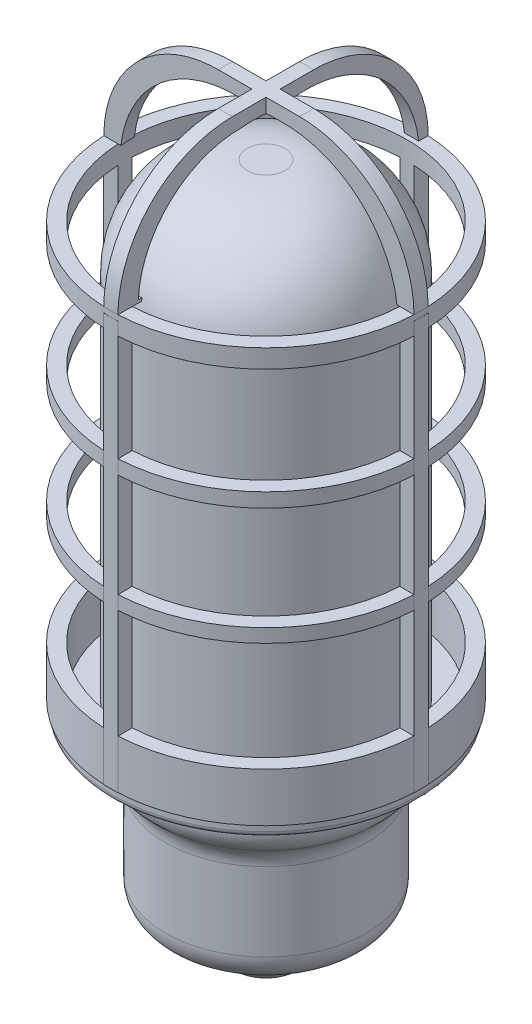
SolidWorks part; units mm, degrees
ref_plane "Front Plane" through (0, 0, 0) normal (0, 0, 1) x (1, 0, 0)
ref_plane "Top Plane" through (0, 0, 0) normal (0, 1, 0) x (1, 0, 0)
ref_plane "Right Plane" through (0, 0, 0) normal (1, 0, 0) x (0, 0, -1)
sketch "Sketch1" plane through (0, 0, 0) normal (0, 1, 0) x (1, 0, 0)
  circle A0 centre (0, 0) radius 72.39
  circle A1 centre (0, 0) radius 65.786
  dimension "D1" = 144.78
  dimension "D2" = 131.572
extrude "Boss-Extrude1" add sketch "Sketch1" along normal blind 22.86
ref_plane "Plane1" through (0, 73.66, 0) normal (0, 1, 0) x (1, 0, 0)
sketch "Sketch2" plane through (0, 73.66, 0) normal (0, 1, 0) x (1, 0, 0)
  circle A0 centre (0, 0) radius 72.39
  dimension "D1" = 144.78
extrude "Boss-Extrude2" add sketch "Sketch2" along normal blind 6.35 separate body
ref_plane "Plane2" through (0, 128.27, 0) normal (0, 1, 0) x (1, 0, 0)
sketch "Sketch3" plane through (0, 128.27, 0) normal (0, 1, 0) x (1, 0, 0)
  circle A0 centre (0, 0) radius 72.39
extrude "Boss-Extrude3" add sketch "Sketch3" along normal blind 6.604 separate body
ref_plane "Plane3" through (0, 184.404, 0) normal (0, 1, 0) x (1, 0, 0)
sketch "Sketch4" plane through (0, 184.404, 0) normal (0, 1, 0) x (1, 0, 0)
  circle A0 centre (0, 0) radius 72.39
extrude "Boss-Extrude4" add sketch "Sketch4" along normal blind 6.096 separate body
sketch "Sketch6" plane through (0, 0, 0) normal (0, -1, 0) x (1, 0, 0)
  circle A0 centre (0, 0) radius 65.786
  dimension "D1" = 131.572
extrude "Cut-Extrude1" cut sketch "Sketch6" against normal through all
ref_plane "Plane4" through (72.39, 0, 0) normal (1, 0, 0) x (0, 0, -1)
sketch "Sketch7" plane through (72.39, 0, 0) normal (1, 0, 0) x (0, 0, -1)
  line L0 (0, 0) -> (0, 190.5) construction
  line L1 (65.786, 190.5) -> (-65.786, 190.5) construction
  line L3 (-3.302, 190.5) -> (-3.302, 0)
  line L4 (-72.39, 0) -> (72.39, 0) construction
  line L5 (-3.302, 0) -> (3.302, 0)
  line L6 (3.302, 0) -> (3.302, 190.5)
  line L7 (72.39, 190.5) -> (-72.39, 190.5) construction
  line L9 (-3.302, 190.5) -> (3.302, 190.5)
  dimension "D1" = 3.302
  dimension "D2" = 6.604
extrude "Boss-Extrude5" add sketch "Sketch7" against normal blind 144.78
ref_plane "Plane5" through (0, 0, 72.39) normal (0, 0, 1) x (1, 0, 0)
sketch "Sketch8" plane through (0, 0, 72.39) normal (0, 0, 1) x (1, 0, 0)
  line L0 (0, 0) -> (0, 190.5) construction
  line L1 (72.3147, 190.5) -> (-72.3147, 190.5) construction
  line L2 (-3.302, 0) -> (3.302, 0)
  line L3 (-72.3147, 0) -> (72.3147, 0) construction
  line L4 (-3.302, 0) -> (-3.302, 190.5)
  line L5 (-3.302, 190.5) -> (3.302, 190.5)
  line L6 (3.302, 190.5) -> (3.302, 0)
  dimension "D1" = 3.302
  dimension "D2" = 6.604
extrude "Boss-Extrude6" add sketch "Sketch8" against normal blind 144.78
sketch "Sketch9" plane through (0, 0, 0) normal (0, -1, 0) x (1, 0, 0)
  circle A0 centre (0, 0) radius 65.786
  dimension "D1" = 131.572
extrude "Cut-Extrude2" cut sketch "Sketch9" against normal through all
sketch "Sketch10" plane through (0, 190.5, 0) normal (0, 1, 0) x (1, 0, 0)
  circle A0 centre (0, 0) radius 72.39
  dimension "D1" = 144.78
extrude "Boss-Extrude7" add sketch "Sketch10" along normal blind 55.88
fillet "Fillet1" radius 53.34 1 edges at (0, 246.38, 72.39)
sketch "Sketch11" plane through (0, 246.38, 0) normal (0, 1, 0) x (1, 0, 0)
  line L0 (0, 0) -> (0, -72.39) construction
  line L1 (0, -72.39) -> (3.302, -72.39) construction
  line L2 (0, 0) -> (72.39, 0) construction
  line L3 (72.39, 0) -> (72.39, -3.302) construction
  line L4 (0, 0) -> (0, -3.302) construction
  line L5 (72.39, -3.302) -> (72.39, -72.39)
  line L6 (72.39, -72.39) -> (3.302, -72.39)
  line L7 (0, 0) -> (3.302, 0) construction
  line L8 (3.302, -3.302) -> (72.39, -3.302)
  line L9 (3.302, -3.302) -> (3.302, -72.39)
  dimension "D1" = 3.302
  dimension "D2" = 3.302
extrude "Cut-Extrude3" cut sketch "Sketch11" against normal blind 53.34
mirror "Mirror1" about plane through (0, 0, 0) normal (1, 0, 0) of "Cut-Extrude3"
mirror "Mirror2" about plane through (0, 0, 0) normal (0, 0, 1) of "Mirror1", "Cut-Extrude3"
sketch "Sketch12" plane through (0, 0, -3.302) normal (0, 0, -1) x (-1, 0, 0)
  line L0 (0, 0) -> (0, 246.38) construction
  line L1 (3.302, 246.38) -> (-3.302, 246.38) construction
  line L2 (0, 246.38) -> (0, 239.776) construction
  line L3 (0, 239.776) -> (6.604, 239.776) construction
  line L4 (6.604, 239.776) -> (6.604, 193.04)
  line L5 (72.3147, 193.04) -> (3.302, 193.04) construction
  line L6 (6.604, 193.04) -> (64.6779, 193.04)
  line L7 (72.3147, 193.04) -> (3.302, 193.04) construction
  line L8 (18.7616, 246.38) -> (3.302, 246.38) construction
  arc A0 (64.6779, 193.04) -> (6.604, 239.776) centre (12.273, 187.371) ccw
  dimension "D3" = 52.7107
  dimension "D4" = 59.009
  dimension "D1" = 6.604
  dimension "D2" = 6.604
revolve "Cut-Revolve1" cut sketch "Sketch12" angle 360 about L0
sketch "Sketch13" plane through (0, 190.5, 0) normal (0, -1, 0) x (1, 0, 0)
  circle A0 centre (0, 0) radius 65.786
  dimension "D1" = 131.572
extrude "Cut-Extrude4" cut sketch "Sketch13" against normal blind 2.54
sketch "Sketch14" plane through (0, 193.04, 0) normal (0, -1, 0) x (1, 0, 0)
  circle A0 centre (0, 0) radius 11.784
  dimension "D1" = 23.568
extrude "Cut-Extrude5" cut sketch "Sketch14" against normal blind 46.736
sketch "Sketch16" plane through (3.302, 0, 0) normal (1, 0, 0) x (0, 0, -1)
  line L0 (0, 0) -> (0, 246.38) construction
  line L1 (3.302, 246.38) -> (-3.302, 246.38) construction
  line L2 (0, 246.38) -> (0, 239.7341) construction
  line L3 (0, 239.7341) -> (-12.7, 239.7341) construction
  line L4 (0, 194.3237) -> (-62.8728, 194.3237) construction
  line L5 (-12.7, 239.7341) -> (-12.7, 194.3237)
  line L6 (-12.7, 194.3237) -> (-62.8728, 194.3237)
  arc A0 (-12.7, 239.7341) -> (-62.8728, 194.3237) centre (-15.0812, 191.9425) ccw
  dimension "D5" = 47.8509
  dimension "D1" = 62.8728
  dimension "D2" = 52.0563
  dimension "D3" = 6.6459
  dimension "D4" = 12.7
extrude "Cut-Extrude6" cut sketch "Sketch16" against normal blind 220.98
sketch "Sketch15" plane through (0, 0, 0) normal (0, 1, 0) x (1, 0, 0)
  circle A0 centre (0, 0) radius 54.61
  dimension "D1" = 109.22
extrude "Boss-Extrude8" add sketch "Sketch15" along normal blind 217.932
fillet "Fillet4" radius 45.72 1 edges at (0, 217.932, 54.61)
sketch "Sketch17" plane through (0, 0, 0) normal (0, -1, 0) x (1, 0, 0)
  circle A0 centre (0, 0) radius 71.501
  dimension "D1" = 143.002
extrude "Boss-Extrude9" add sketch "Sketch17" along normal blind 5.588
fillet "Fillet5" radius 2.54 1 edges at (0, -5.588, -71.501)
sketch "Sketch18" plane through (0, -5.588, 0) normal (0, -1, 0) x (1, 0, 0)
  circle A0 centre (0, 0) radius 55.88
  dimension "D1" = 111.76
extrude "Boss-Extrude10" add sketch "Sketch18" along normal blind 21.7424
sketch "Sketch19" plane through (0, -27.3304, 0) normal (0, -1, 0) x (1, 0, 0)
  circle A0 centre (0, 0) radius 46.99
  dimension "D1" = 93.98
extrude "Boss-Extrude11" add sketch "Sketch19" along normal blind 57.658
sketch "Sketch20" plane through (0, -84.9884, 0) normal (0, -1, 0) x (1, 0, 0)
  circle A0 centre (0, 0) radius 19.05
  dimension "D1" = 38.1
extrude "Boss-Extrude12" add sketch "Sketch20" along normal blind 18.796
fillet "Fillet6" radius 12.7 1 edges at (0, -27.3304, -55.88)
fillet "Fillet7" radius 12.7 1 edges at (0, -27.3304, -46.99)
fillet "Fillet8" radius 13.97 2 edges at (0, -84.9884, -46.99) (0, -84.9884, -19.05)
sketch "Sketch21" plane through (0, -103.7844, 0) normal (0, -1, 0) x (1, 0, 0)
  circle A0 centre (0, 0) radius 12.319
  dimension "D1" = 24.638
extrude "Cut-Extrude7" cut sketch "Sketch21" against normal blind 101.6
fillet "Fillet9" radius 13.97 1 edges at (0, -103.7844, -19.05)
